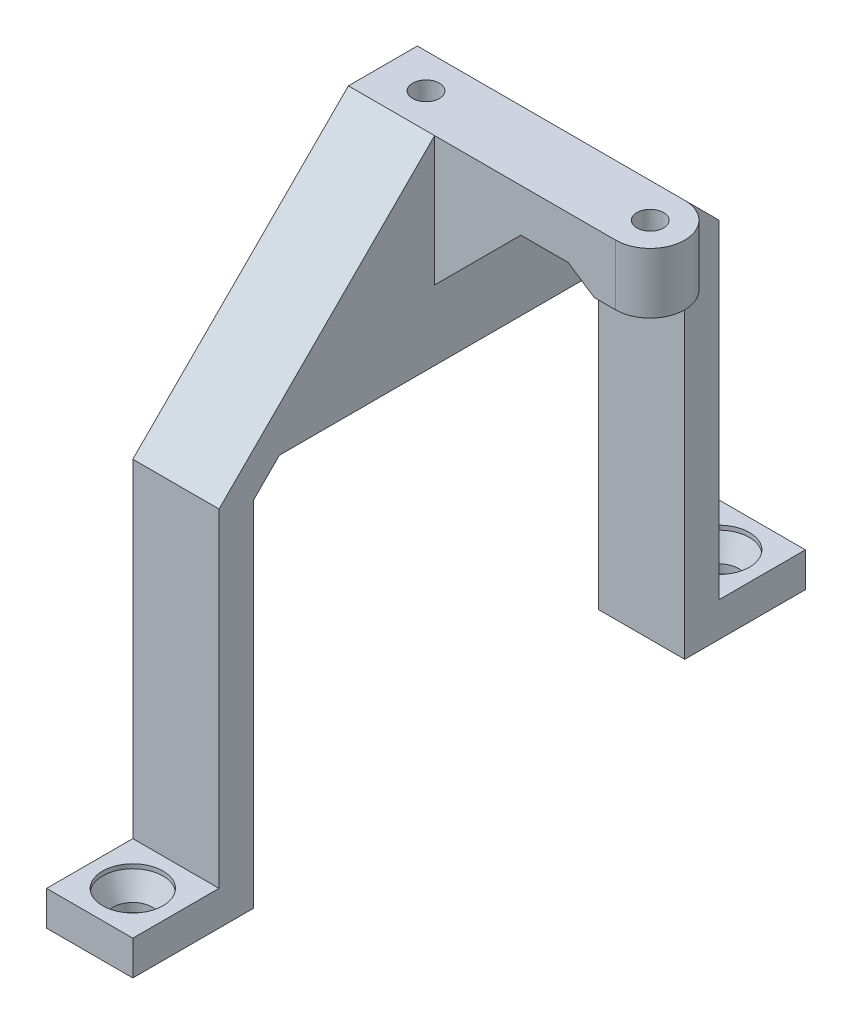
SolidWorks part; units mm, degrees
ref_plane "Front Plane" through (0, 0, 0) normal (0, 0, 1) x (1, 0, 0)
ref_plane "Top Plane" through (0, 0, 0) normal (0, 1, 0) x (1, 0, 0)
ref_plane "Right Plane" through (0, 0, 0) normal (1, 0, 0) x (0, 0, -1)
sketch "Sketch1" plane through (0, 0, 0) normal (0, 1, 0) x (1, 0, 0)
  line L0 (0, 4) -> (-31, 4)
  line L1 (0, -4) -> (-31, -4)
  line L3 (-31, 4) -> (-31, -4)
  line L4 (0, 0) -> (-26, 0) construction
  circle A0 centre (0, 0) radius 1.55
  arc A1 (0, -4) -> (0, 4) centre (0, 0) ccw
  arc A2 (0, 4) -> (0, -4) centre (0, 0) ccw construction
  circle A5 centre (-26, 0) radius 1.55
  dimension "D1" = 3.1
  dimension "D2" = 8
  dimension "D4" = 3.1
  dimension "D3" = 26
  dimension "D5" = 5
extrude "Boss-Extrude1" add sketch "Sketch1" along normal blind 5 contours L0 L1 A1 A5 A0 region at (-13.9712, 0, 0)
sketch "Sketch2" plane through (0, 0, 0) normal (0, -1, 0) x (1, 0, 0)
  line L0 (0, 4) -> (-2.5, 4)
  line L2 (-2.5, 4) -> (-2.5, -4)
  line L4 (-2.5, -4) -> (0, -4)
  line L6 (0, 4) -> (-31, 4) construction
  arc A0 (0, -4) -> (0, 4) centre (0, 0) ccw
  arc A1 (0, 4) -> (-4, 0) centre (0, 0) ccw construction
  arc A2 (-4, 0) -> (0, -4) centre (0, 0) ccw construction
  circle A3 centre (0, 0) radius 1.55
  circle A5 centre (0, 0) radius 1.55 construction
  arc A6 (0, -4) -> (0, 4) centre (0, 0) ccw construction
  dimension "D1" = 2.5
extrude "Boss-Extrude2" add sketch "Sketch2" along normal blind 2 contours A0 L0 L2 L4 | A3
chamfer "Chamfer1" distance 3 distance2 2 1 edges at (-2.5, 0, 0) first distance on face at (-26, 0, 1.55)
sketch "Sketch3" plane through (0, 0, 0) normal (0, -1, 0) x (1, 0, 0)
  line L0 (-5.5, -4) -> (-31, -4) construction
  line L1 (-31, 4) -> (-21, 4)
  line L2 (-31, 4) -> (-31, -4)
  line L3 (-31, -4) -> (-21, -4)
  line L4 (-21, 4) -> (-21, -4)
  circle A0 centre (-26, 0) radius 1.55
  dimension "D1" = 5
extrude "Boss-Extrude3" add sketch "Sketch3" along normal blind 18.1
sketch "Sketch4" plane through (-31, 0, 0) normal (-1, 0, 0) x (0, 0, 1)
  line L0 (0, -18.1) -> (-25, -18.1) construction
  line L1 (4, -18.1) -> (-4, -18.1) construction
  line L2 (-25, -18.1) -> (-25, -24.1) construction
  line L3 (-25, -21.1) -> (-4, -0.1) construction
  line L4 (-4, 5) -> (-4, -18.1) construction
  line L5 (-4, -18.1) -> (-22, -18.1)
  line L6 (-22, -18.1) -> (-25, -21.1)
  line L7 (-25, -21.1) -> (-25, -62.1)
  line L8 (-29, -20) -> (-4, 5)
  line L9 (-29, -20) -> (-29, -58.1)
  line L10 (-29, -58.1) -> (-39, -58.1)
  line L11 (-39, -58.1) -> (-39, -62.1)
  line L12 (-39, -62.1) -> (-25, -62.1)
  line L13 (-4, 5) -> (-4, -18.1)
  dimension "D1" = 25
  dimension "D2" = 6
  dimension "D3" = 45
  dimension "D4" = 41
  dimension "D5" = 4
  dimension "D7" = 4
  dimension "D8" = 10
extrude "Boss-Extrude4" add sketch "Sketch4" against normal up to vertex (10 mm away) up to point (-21, 0, -4)
mirror "Mirror1" about plane through (0, 0, 0) normal (0, 0, 1) of "Boss-Extrude4"
chamfer "Chamfer2" distance 10 angle 45 1 edges at (-21, 0, 0)
sketch "Sketch5" plane through (-21, 0, 0) normal (1, 0, 0) x (0, 0, -1)
  line L0 (22, -18.1) -> (-22, -18.1) construction
  line L1 (0, 5) -> (0, -18.1) construction
  line L2 (0, -13.6) -> (50000, -13.6) construction
  line L3 (-8, -13.6) -> (-8, 49986.4) construction
  line L4 (-16, -13.6) -> (-16, 49986.4) construction
  line L5 (0, 5) -> (0, -2) construction
  line L7 (-8, -5.6) -> (49992, -5.6) construction
  line L8 (0, 12.705) -> (0, -12.705) construction
  circle A0 centre (0, -13.6) radius 2.5
  circle A1 centre (-8, -13.6) radius 2.5
  circle A2 centre (-16, -13.6) radius 2.5
  circle A3 centre (-8, -5.6) radius 2.5
  circle A4 centre (16, -13.6) radius 2.5
  circle A5 centre (8, -13.6) radius 2.5
  circle A6 centre (8, -5.6) radius 2.5
  circle A7 centre (0, -5.6) radius 2.5
  dimension "D1" = 5
  dimension "D5" = 5
  dimension "D6" = 8
  dimension "D7" = 5
  dimension "D8" = 5
  dimension "D2" = 4.5
  dimension "D3" = 8
  dimension "D4" = 8
extrude "Cut-Extrude1" [suppressed] cut sketch "Sketch5" against normal through all both and the other way through all
sketch "Sketch6" plane through (0, -58.1, 0) normal (0, 1, 0) x (1, 0, 0)
  line L2 (-31, -34) -> (-21, -34) construction
  line L3 (-31, -29) -> (-31, -39) construction
  line L4 (-21, -29) -> (-21, -39) construction
  line L5 (-26, -39) -> (-26, -29) construction
  line L6 (-21, -39) -> (-31, -39) construction
  line L7 (-21, -29) -> (-31, -29) construction
  circle A0 centre (-26, -34) radius 2.25
  dimension "D3" = 4.5
extrude "Cut-Extrude2" cut sketch "Sketch6" against normal through all
sketch "Sketch7" plane through (0, -58.1, 0) normal (0, 1, 0) x (1, 0, 0)
  circle A0 centre (-26, -34) radius 3.5
  dimension "D1" = 7
extrude "Cut-Extrude3" cut sketch "Sketch7" against normal blind 3
chamfer "Chamfer3" distance 2.5 distance2 1.25 1 edges at (-26, -61.1, 37.5) first distance on face at (-26, -61.1, 37.5)
mirror "Mirror2" about plane through (0, 0, 0) normal (0, 0, 1) of "Cut-Extrude2", "Cut-Extrude3", "Chamfer3"
sketch "Sketch8" [suppressed] plane through (-31, 0, 0) normal (-1, 0, 0) x (0, 0, 1)
  line L0 (-4, 5) -> (-4, -0.6)
  line L1 (-4, -0.6) -> (-9.6, -0.6)
  line L2 (-4, 5) -> (-29, -20) construction
  line L3 (-9.6, -0.6) -> (-4, 5)
  line L4 (4, 5) -> (4, -0.6)
  line L5 (4, -0.6) -> (9.6, -0.6)
  line L6 (4, 5) -> (29, -20) construction
  line L7 (9.6, -0.6) -> (4, 5)
  circle A0 centre (-8, -5.6) radius 2.5 construction
  circle A1 centre (8, -5.6) radius 2.5 construction
  dimension "D1" = 5
  dimension "D2" = 5
extrude "Cut-Extrude4" [suppressed] cut sketch "Sketch8" against normal through all
chamfer "Chamfer4" [suppressed] distance 0.5 angle 45
